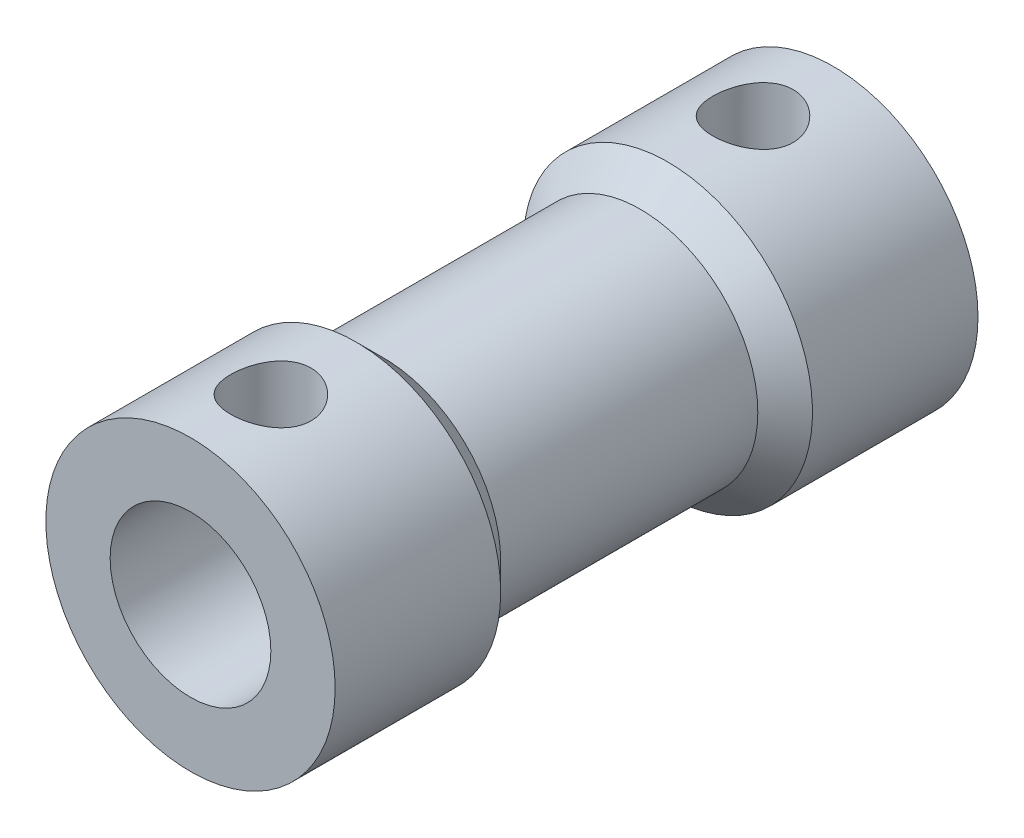
SolidWorks part; units mm, degrees
ref_plane "前基準面" through (0, 0, 0) normal (0, 0, 1) x (1, 0, 0)
ref_plane "上基準面" through (0, 0, 0) normal (0, 1, 0) x (1, 0, 0)
ref_plane "右基準面" through (0, 0, 0) normal (1, 0, 0) x (0, 0, -1)
ref_axis "基準軸1" through (0, -55, 0) along (0, 1, 0)
ref_axis "基準軸2" through (-88.99, 0, 0) along (1, 0, 0)
ref_axis "基準軸3" through (0, 0, 55) along (0, 0, -1)
sketch "草圖1" plane through (0, 0, 0) normal (0, 0, 1) x (1, 0, 0)
  circle A0 centre (0, 0) radius 4.5
  dimension "D1" = 9
extrude "填料-伸長1" add sketch "草圖1" along normal blind 5
sketch "草圖2" plane through (0, 0, 5) normal (0, 0, 1) x (1, 0, 0)
  circle A0 centre (0, 0) radius 3.65
  dimension "D1" = 7.3
extrude "填料-伸長2" add sketch "草圖2" along normal blind 10
sketch "草圖3" plane through (0, 0, 15) normal (0, 0, 1) x (1, 0, 0)
  circle A0 centre (0, 0) radius 4.5
  dimension "D1" = 9
extrude "填料-伸長3" add sketch "草圖3" along normal blind 5
chamfer "導角2" distance 1 angle 45 1 edges at (3.65, 0, 5)
chamfer "導角3" distance 1 angle 45 1 edges at (3.65, 0, 15)
hole_wizard "Ø5.0 (5) 直徑孔1" positions "草圖4" profile "草圖5" hole size "Ø5.0" standard "Ansi Metric"
sketch "草圖4" plane through (0, 0, 20) normal (0, 0, 1) x (1, 0, 0)
  line L0 (4.95, 0) -> (-4.95, 0) construction
  line L1 (0, -4.95) -> (0, 4.95) construction
  point P0 (0, 0)
  point P7 (0, 0)
  dimension "D1" = 0
  dimension "D2" = 0
sketch "草圖5" plane through (0, 0, 20) normal (1, 0, 0) x (0, -1, 0)
  line L0 (0, 0) -> (0, 6.5022)
  line L1 (0, 6.5022) -> (2.5, 5)
  line L2 (2.5, 5) -> (2.5, 0)
  line L5 (2.5, 0) -> (0, 0)
  line L10 (0, 6.5022) -> (-2.5, 5) construction
  line L11 (0, -6.35) -> (0, 107.95) construction
  dimension "苝ふ 畖" = 5
  dimension "苝ふ瞏 " = 5
  dimension "旧繷à " = 118
hole_wizard "Ø3.0 (3) 直徑孔1" positions "草圖6" profile "草圖7" hole size "Ø3.0" standard "Ansi Metric"
sketch "草圖6" plane through (0, 0, 0) normal (0, 0, -1) x (-1, 0, 0)
  line L0 (0, 4.95) -> (0, -4.95) construction
  line L1 (4.95, 0) -> (-4.95, 0) construction
  point P0 (0, 0)
  dimension "D1" = 0
  dimension "D2" = 0
sketch "草圖7" plane through (0, 0, 0) normal (1, 0, 0) x (0, 1, 0)
  line L0 (0, 0) -> (0, 5.9013)
  line L1 (0, 5.9013) -> (1.5, 5)
  line L2 (1.5, 5) -> (1.5, 0)
  line L5 (1.5, 0) -> (0, 0)
  line L10 (0, 5.9013) -> (-1.5, 5) construction
  line L11 (0, -6.35) -> (0, 107.95) construction
  dimension "苝ふ 畖" = 3
  dimension "苝ふ瞏 " = 5
  dimension "旧繷à " = 118
ref_plane "平面1" through (0, 4.5, 0) normal (0, 1, 0) x (1, 0, 0)
hole_wizard "M3x0.5  螺絲攻的螺孔鑽1" positions "草圖8" profile "草圖9" hole size "M3x0.5" standard "Ansi Metric" end condition up to next
sketch "草圖8" plane through (0, 4.5, 0) normal (0, 1, 0) x (1, 0, 0)
  line L0 (0, -4.95) -> (0, 4.95) construction
  line L1 (-4.95, 0) -> (4.95, 0) construction
  point P0 (0, -2.5)
  dimension "D1" = 0
  dimension "D2" = 2.5
sketch "草圖9" plane through (0, 4.5, 2.5) normal (1, 0, 0) x (0, 0, 1)
  line L0 (0, 0) -> (0, 9)
  line L1 (0, 9) -> (1.25, 9)
  line L2 (1.25, 9) -> (1.25, 0)
  line L5 (1.25, 0) -> (0, 0)
  line L11 (0, -6.35) -> (0, 107.95) construction
  dimension "砮 ふ 畖" = 2.5
  dimension "砮 ふ瞏 " = 9
ref_plane "平面2" through (0, 0, 10) normal (0, 0, -1) x (-1, 0, 0)
mirror "鏡射1" about plane through (0, 0, 10) normal (0, 0, -1) of "M3x0.5  螺絲攻的螺孔鑽1"
